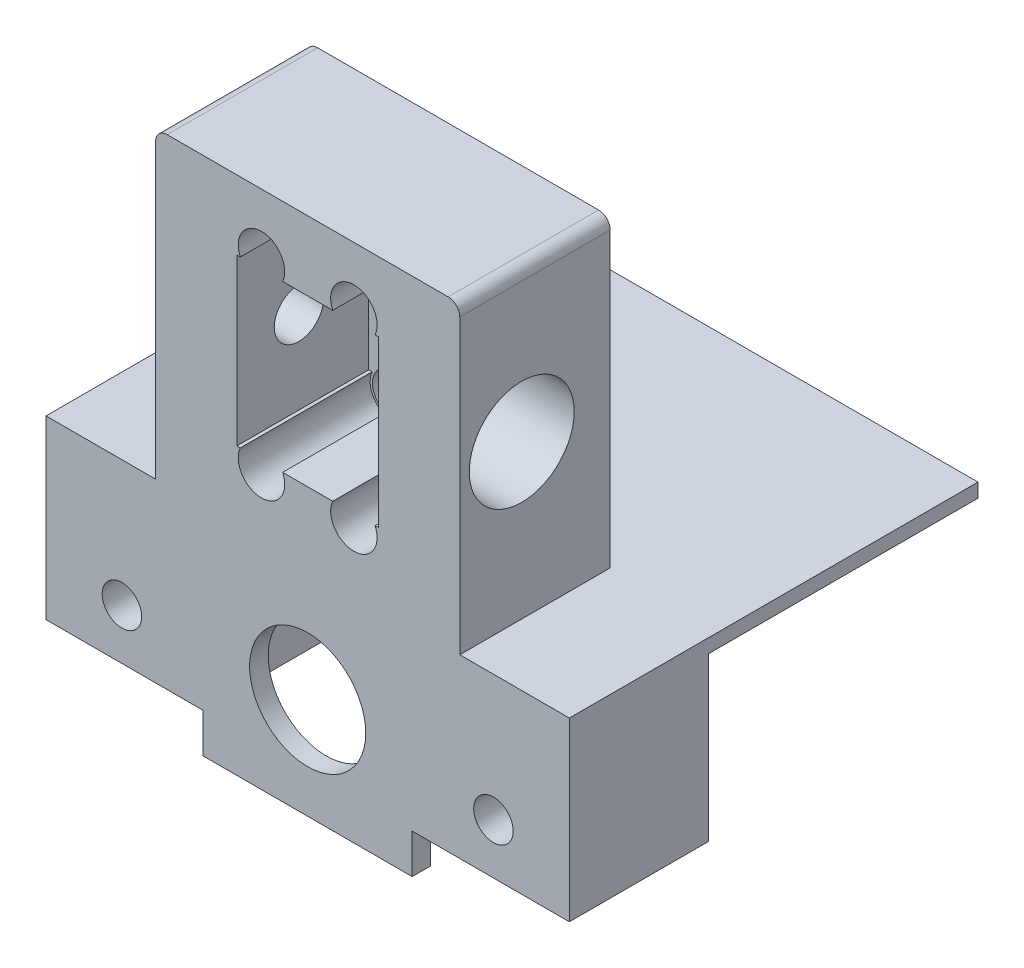
SolidWorks part; units mm, degrees
ref_plane "Front Plane" through (0, 0, 0) normal (0, 0, 1) x (1, 0, 0)
ref_plane "Top Plane" through (0, 0, 0) normal (0, 1, 0) x (1, 0, 0)
ref_plane "Right Plane" through (0, 0, 0) normal (1, 0, 0) x (0, 0, -1)
sketch "Sketch1" plane through (0, 0, 0) normal (0, 0, 1) x (1, 0, 0)
  line L1 (0, 0) -> (-65.5, 0)
  line L2 (0, 0) -> (0, -65.5)
  line L3 (0, -65.5) -> (-65.5, -65.5)
  line L4 (-65.5, 0) -> (-65.5, -65.5)
  line L5 (-17.5, -14.95) -> (-48, -14.95)
  line L6 (-17.5, -14.95) -> (-17.5, -50.55)
  line L7 (-17.5, -50.55) -> (-48, -50.55)
  line L8 (-48, -14.95) -> (-48, -50.55)
  point P10 (-32.75, -14.95)
  point P11 (-48, -32.75)
  point P12 (-65.5, -32.75)
  point P13 (-32.75, 0)
  dimension "D1" = 65.5
  dimension "D2" = 35.6
  dimension "D3" = 30.5
extrude "Boss-Extrude1" add sketch "Sketch1" along normal blind 28.4 and the other way blind 4
sketch "Sketch5" plane through (0, 0, 0) normal (1, 0, 0) x (0, 0, -1)
  line L2 (4, -65.5) -> (4, 0) construction
  line L4 (4, 0) -> (-28.4, 0) construction
  circle A1 centre (-15.05, -32.45) radius 11.3
  dimension "D1" = 11.3
  dimension "D2" = 19.05
  dimension "D3" = 32.45
extrude "Cut-Extrude1" cut sketch "Sketch5" against normal up to next
sketch "Sketch7" plane through (-65.5, 0, 0) normal (1, 0, 0) x (0, 0, -1)
  circle A1 centre (-15.05, -32.45) radius 5.3
  circle A3 centre (-15.05, -32.45) radius 11.3 construction
  circle A4 centre (-15.05, -32.45) radius 11.3 construction
  dimension "D1" = 5.3
extrude "Cut-Extrude4" cut sketch "Sketch7" along normal up to next
sketch "Sketch8" plane through (0, 0, -4) normal (0, 0, -1) x (-1, 0, 0)
  line L4 (17.5, -14.95) -> (17.5, -50.55)
  line L5 (48, -14.95) -> (17.5, -14.95)
  line L6 (48, -50.55) -> (48, -14.95)
  line L7 (17.5, -50.55) -> (48, -50.55)
  line L8 (17.5, -14.95) -> (17.5, -50.55)
  line L9 (48, -14.95) -> (17.5, -14.95)
  line L10 (48, -50.55) -> (48, -14.95)
  line L11 (17.5, -50.55) -> (48, -50.55)
  dimension "D2" = 30.5
  dimension "D3" = 35.6
  dimension "D1" = 0
extrude "Boss-Extrude2" add sketch "Sketch8" against normal blind 4
sketch "Sketch9" plane through (0, 0, -4) normal (0, 0, 1) x (1, 0, 0)
  line L0 (0, 0) -> (-65.5, 0) construction
  line L1 (0, 0) -> (0, -65.5) construction
  line L2 (0, -65.5) -> (-65.5, -65.5) construction
  line L3 (-32.75, -65.5) -> (-32.75, 0) construction
  line L4 (0, -32.75) -> (-65.5, -32.75) construction
  line L5 (-65.5, 0) -> (-65.5, -65.5) construction
  line L6 (-32.75, -65.5) -> (-32.75, -53.5) construction
  line L7 (-65.5, -65.5) -> (0, 0) construction
  circle A0 centre (-12.75, -12.9) radius 4.9
  circle A1 centre (-52.75, -12.9) radius 4.9
  circle A2 centre (-52.75, -52.6) radius 4.9
  circle A3 centre (-12.75, -52.6) radius 4.9
  point P20 (-32.75, -12)
  point P26 (-12, -32.75)
  point P27 (-53.5, -32.75)
  dimension "D3" = 9.8
  dimension "D1" = 12.9
  dimension "D2" = 12.75
  dimension "D4" = 12
extrude "Cut-Extrude5" cut sketch "Sketch9" along normal blind 2.2
fillet "Fillet1" radius 2.5 2 edges at (0, 0, 12.2) (-65.5, 0, 12.2)
sketch "Sketch10" plane through (0, 0, 0) normal (0, 0, 1) x (1, 0, 0)
  line L0 (0, -52.6) -> (-22.8, -52.6) construction
  line L1 (0, 0) -> (0, -65.5) construction
  line L2 (-22.8, -52.6) -> (-22.8, -65.5) construction
  line L3 (0, -65.5) -> (-65.5, -65.5) construction
  line L5 (-32.75, -65.5) -> (-32.75, 0) construction
  line L6 (0, -32.75) -> (-65.5, -32.75) construction
  line L7 (-32.75, -65.5) -> (-32.75, 0) construction
  line L8 (0, -32.75) -> (-65.5, -32.75) construction
  circle A0 centre (-22.8, -12.9) radius 5
  circle A1 centre (-42.7, -12.9) radius 5
  circle A2 centre (-22.8, -52.6) radius 5
  circle A3 centre (-42.7, -52.6) radius 5
  point P7 (-22.8, -12.9)
  point P8 (-42.7, -12.9)
  point P13 (-42.7, -52.6)
  dimension "D3" = 10
  dimension "D1" = 22.8
  dimension "D2" = 12.9
extrude "Cut-Extrude7" cut sketch "Sketch10" along normal up to next
sketch "Sketch20" plane through (0, 0, 0) normal (0, 0, 1) x (1, 0, 0)
  line L0 (-32.75, 0) -> (-32.75, -65.5) construction
  line L1 (-32.75, -65.5) -> (-32.75, 0) construction
  line L2 (-65.5, -32.75) -> (0, -32.75) construction
  line L3 (0, -32.75) -> (-65.5, -32.75) construction
  line L4 (-62.12, -65.5) -> (-3.38, -65.5) construction
  line L5 (0, -65.5) -> (-65.5, -65.5) construction
  line L6 (0, 0) -> (-65.5, 0) construction
  line L7 (0, 0) -> (0, -65.5) construction
  line L8 (-65.5, 0) -> (-65.5, -65.5) construction
  arc A0 (-38.1396, -14.95) -> (-47.2604, -14.95) centre (-42.7, -12.9) ccw construction
  point P0 (-42.7, -12.9)
  point P13 (-22.8, -12.9)
  point P15 (-22.8, -52.6)
  point P16 (-42.7, -52.6)
hole_wizard "CBORE for M4 Pan Head Machine Screw1" positions "3DSketch5" profile "Sketch22" counterbore size "M4" standard "ANSI Metric"
sketch3d "3DSketch5"
  point P0 (-42.7, -12.9, 0)
  point P3 (-22.8, -12.9, 0)
  point P6 (-42.7, -52.6, 0)
  point P9 (-22.8, -52.6, 0)
sketch "Sketch22" plane through (-42.7, -12.9, 0) normal (1, 0, 0) x (0, -1, 0)
  line L0 (0, 0) -> (0, 9.4421)
  line L1 (0, 9.4421) -> (2.4, 8)
  line L2 (2.4, 8) -> (2.4, 3.1)
  line L3 (2.4, 3.1) -> (4.5, 3.1)
  line L4 (4.5, 3.1) -> (4.5, 0)
  line L5 (4.5, 0) -> (0, 0)
  line L10 (0, 9.4421) -> (-2.4, 8) construction
  line L11 (0, -6.35) -> (0, 107.95) construction
  dimension "Hole Dia." = 4.8
  dimension "Hole Depth" = 8
  dimension "C'Bore Dia." = 9
  dimension "C'Bore Depth" = 3.1
  dimension "Drill Angle" = 118
sketch "Sketch23" plane through (0, -65.5, 0) normal (0, -1, 0) x (1, 0, 0)
  line L1 (23.6, 28.4) -> (-89.1, 28.4)
  line L2 (23.6, 28.4) -> (23.6, -59.6)
  line L3 (23.6, -59.6) -> (-89.1, -59.6)
  line L4 (-89.1, 28.4) -> (-89.1, -59.6)
  line L9 (-65.5, 28.4) -> (0, 28.4) construction
  point P4 (-32.75, -59.6)
  dimension "D1" = 88
  dimension "D2" = 112.7
extrude "Boss-Extrude3" add sketch "Sketch23" along normal blind 3
sketch "Sketch24" plane through (0, -68.5, 0) normal (0, -1, 0) x (-1, 0, 0)
  line L0 (-23.6, -28.4) -> (89.1, -28.4) construction
  line L1 (55.25, -28.4) -> (10.25, -28.4)
  line L2 (55.25, -28.4) -> (55.25, -24.4)
  line L3 (55.25, -24.4) -> (10.25, -24.4)
  line L4 (10.25, -28.4) -> (10.25, -24.4)
  point P6 (32.75, -28.4)
  dimension "D1" = 4
  dimension "D2" = 45
extrude "Boss-Extrude4" add sketch "Sketch24" along normal blind 43.5
sketch "Sketch25" plane through (0, 0, 28.4) normal (0, 0, 1) x (1, 0, 0)
  line L1 (-55.25, -68.5) -> (-89.1, -68.5) construction
  line L2 (-32.75, -112) -> (-32.75, 0) construction
  line L3 (-10.25, -112) -> (-55.25, -112) construction
  line L4 (-2.5, 0) -> (-63, 0) construction
  point P0 (-48.25, -74.5)
  point P5 (-48.25, -105.5)
  dimension "D1" = 15.5
  dimension "D2" = 6
  dimension "D3" = 31
sketch "Sketch28" plane through (0, 0, 28.4) normal (0, 0, 1) x (1, 0, 0)
  line L0 (-10.25, -112) -> (-55.25, -68.5) construction
  circle A0 centre (-32.75, -90.25) radius 22.0978
  circle A1 centre (-32.75, -90.25) radius 12.5
  dimension "D1" = 25
ref_plane "Plane1" through (-32.75, 0, 0) normal (1, 0, 0) x (0, 0, -1)
extrude "Cut-Extrude8" cut sketch "Sketch28" against normal up to next contours A1
sketch "Sketch29" plane through (0, 0, 28.4) normal (0, 0, 1) x (1, 0, 0)
  line L0 (-32.75, -89.65) -> (-55.25, -89.65) construction
  line L1 (-55.25, -112) -> (-55.25, -68.5) construction
sketch "Sketch30" plane through (0, -68.5, 0) normal (0, -1, 0) x (-1, 0, 0)
  line L1 (55.25, -28.4) -> (89.1, -28.4)
  line L2 (55.25, -28.4) -> (55.25, 1.6)
  line L3 (55.25, 1.6) -> (89.1, 1.6)
  line L4 (89.1, -28.4) -> (89.1, 1.6)
  line L5 (89.1, -28.4) -> (89.1, 59.6) construction
  dimension "D1" = 30
extrude "Boss-Extrude5" add sketch "Sketch30" along normal blind 35
sketch "Sketch31" plane through (0, 0, 28.4) normal (0, 0, 1) x (1, 0, 0)
  line L0 (-72.75, -92.65) -> (-72.75, -103.5) construction
  line L1 (-55.25, -103.5) -> (-89.1, -103.5) construction
  circle A0 centre (-72.75, -92.65) radius 4.25
  dimension "D3" = 8.5
  dimension "D1" = 3
  dimension "D2" = 40
sketch "Sketch33" plane through (0, -103.5, 0) normal (0, -1, 0) x (-1, 0, 0)
  line L0 (72.75, -28.4) -> (72.75, 1.6) construction
  line L1 (89.1, 1.6) -> (55.25, 1.6) construction
  point P5 (72.75, -13.4)
  point P6 (72.75, -21.4)
  point P7 (72.75, -5.4)
  dimension "D1" = 8
  dimension "D2" = 8
extrude "Cut-Extrude10" cut sketch "Sketch31" against normal up to next
hole_wizard "CBORE for M3 Pan Head Machine Screw2" positions "Sketch34" profile "Sketch35" counterbore size "M3" standard "ANSI Metric" end condition up to next
sketch "Sketch34" plane through (0, -103.5, 0) normal (0, -1, 0) x (-1, 0, 0)
  point P0 (72.75, -13.4)
sketch "Sketch35" plane through (-72.75, -103.5, 13.4) normal (1, 0, 0) x (0, 0, -1)
  line L0 (0, 0) -> (0, 6.6)
  line L1 (0, 6.6) -> (1.6, 6.6)
  line L3 (1.6, 6.6) -> (1.6, 2.4)
  line L4 (1.6, 2.4) -> (3.5, 2.4)
  line L5 (3.5, 2.4) -> (3.5, 0)
  line L7 (3.5, 0) -> (0, 0)
  line L11 (0, -6.35) -> (0, 107.95) construction
  dimension "Thru Hole Dia." = 3.2
  dimension "Thru Hole Depth" = 6.6
  dimension "C'Bore Dia." = 7
  dimension "C'Bore Depth" = 2.4
mirror "Mirror2" about plane through (-32.75, 0, 0) normal (1, 0, 0) of "Cut-Extrude10", "CBORE for M3 Pan Head Machine Screw2", "Boss-Extrude5"
